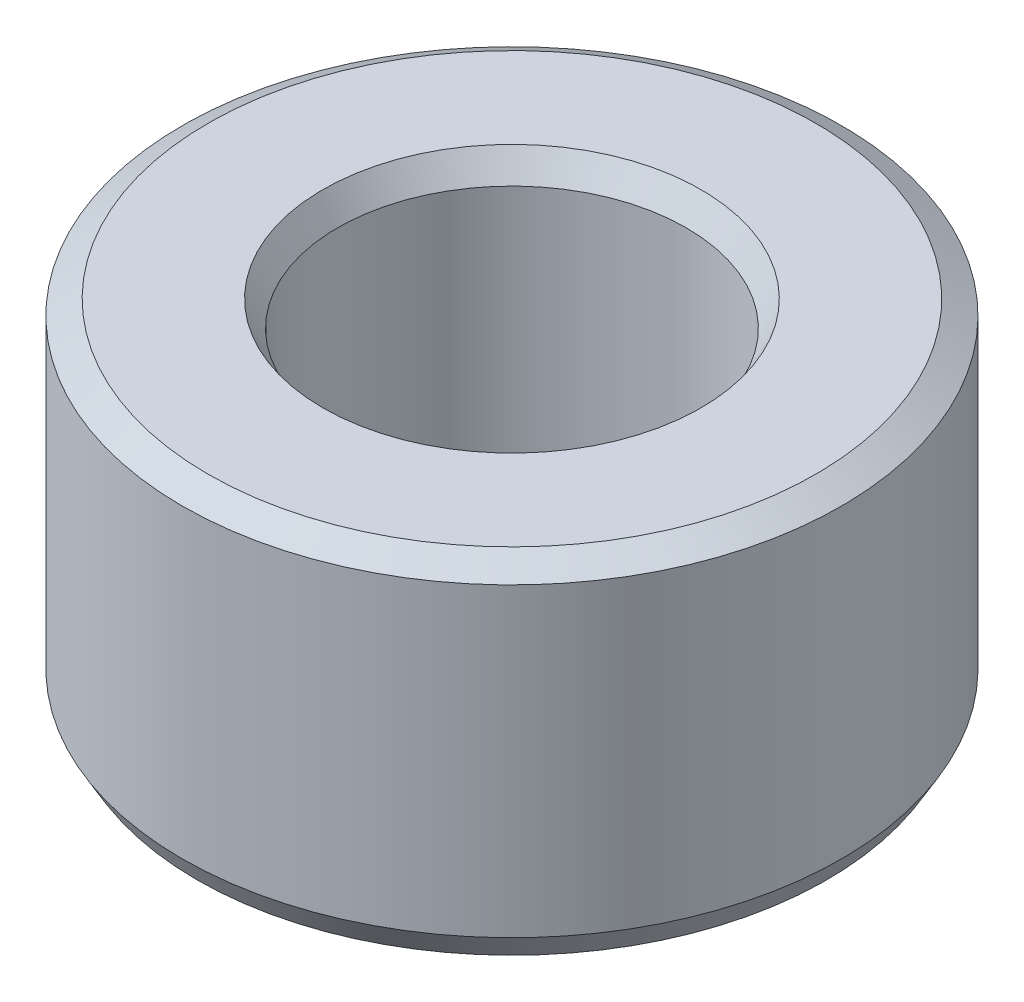
SolidWorks part; units mm, degrees
ref_plane "Front Plane" through (0, 0, 0) normal (0, 0, 1) x (1, 0, 0)
ref_plane "Top Plane" through (0, 0, 0) normal (0, 1, 0) x (1, 0, 0)
ref_plane "Right Plane" through (0, 0, 0) normal (1, 0, 0) x (0, 0, -1)
sketch "Sketch1" plane through (0, 0, 0) normal (0, 1, 0) x (1, 0, 0)
  circle A0 centre (0, 0) radius 42.5
  dimension "SLEEVE_OD" = 85
extrude "Boss-Extrude1" add sketch "Sketch1" along normal blind 44.6188
sketch "Sketch2" plane through (0, 0, 0) normal (0, 1, 0) x (1, 0, 0)
  circle A0 centre (0, 0) radius 22.4736
  dimension "BORE_D" = 44.9471
extrude "Cut-Extrude1" cut sketch "Sketch2" along normal through all
chamfer "Chamfer1" distance 1.9095 angle 60 4 edges at (0, 44.6188, 22.4736) (0, 0, 22.4736) (0, 0, 42.5) (0, 44.6188, 42.5) first distance on face at (0, 44.6188, 22.4736) first distance on face at (0, 0, 22.4736) first distance on face at (0, 44.6188, 42.5)
